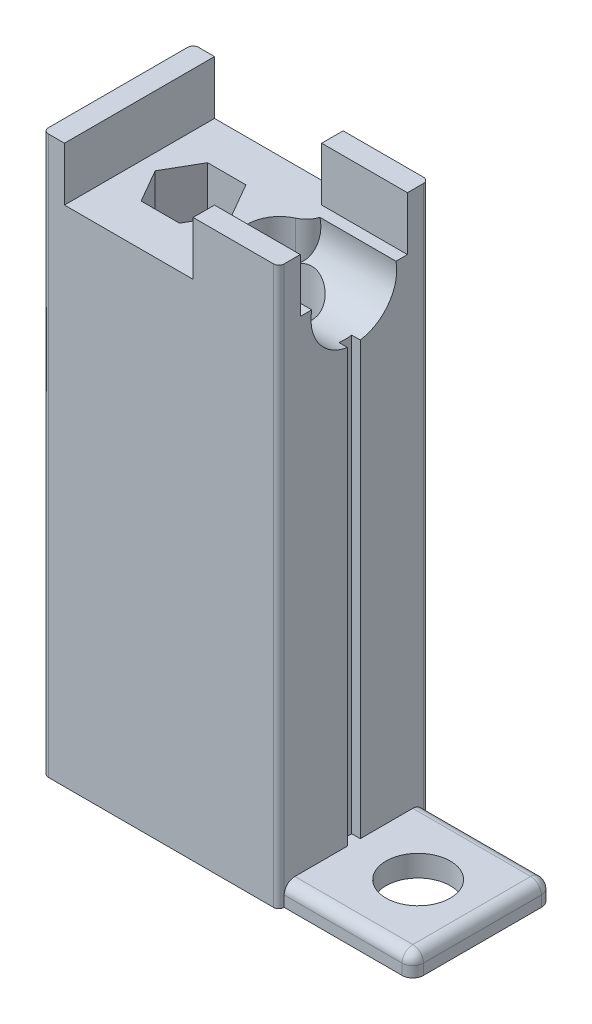
SolidWorks part; units mm, degrees
ref_plane "Front Plane" through (0, 0, 0) normal (0, 0, 1) x (1, 0, 0)
ref_plane "Top Plane" through (0, 0, 0) normal (0, 1, 0) x (1, 0, 0)
ref_plane "Right Plane" through (0, 0, 0) normal (1, 0, 0) x (0, 0, -1)
sketch "Sketch1" plane through (0, 0, 0) normal (0, 1, 0) x (1, 0, 0)
  line L1 (0, 0) -> (22, 0)
  line L2 (0, 0) -> (0, 14)
  line L3 (0, 14) -> (22, 14)
  line L4 (22, 0) -> (22, 14)
  dimension "D1" = 22
  dimension "D2" = 14
extrude "Boss-Extrude1" add sketch "Sketch1" along normal blind 47
sketch "Sketch2" plane through (0, 47, 0) normal (0, 1, 0) x (1, 0, 0)
  line L0 (22, 0) -> (22, 2)
  line L1 (22, 0) -> (22, 14) construction
  line L2 (0, 14) -> (2, 14)
  line L3 (22, 14) -> (0, 14) construction
  line L4 (2, 14) -> (2, 0)
  line L5 (22, 12) -> (22, 14)
  line L6 (0, 0) -> (22, 0) construction
  line L7 (0, 14) -> (0, 0)
  line L8 (2, 0) -> (0, 0)
  line L9 (22, 14) -> (14, 14)
  line L10 (14, 14) -> (14, 12)
  line L11 (14, 12) -> (22, 12)
  line L12 (22, 2) -> (14, 2)
  line L13 (14, 2) -> (14, 0)
  line L14 (14, 0) -> (22, 0)
  dimension "D1" = 2
  dimension "D2" = 2
  dimension "D3" = 8
  dimension "D4" = 8
  dimension "D5" = 2
extrude "Boss-Extrude2" add sketch "Sketch2" along normal blind 5
sketch "Sketch3" plane through (0, 47, 0) normal (0, 1, 0) x (1, 0, 0)
  line L1 (2, 0) -> (2, 14) construction
  line L2 (0, 7) -> (22, 7) construction
  line L4 (0, 14) -> (0, 0) construction
  line L5 (22, 2) -> (22, 12) construction
  line L7 (10.621, 7) -> (8.8312, 10.1)
  line L8 (8.8312, 10.1) -> (5.2517, 10.1)
  line L9 (5.2517, 10.1) -> (3.4619, 7)
  line L10 (3.4619, 7) -> (5.2517, 3.9)
  line L13 (5.2517, 3.9) -> (8.8312, 3.9)
  line L14 (8.8312, 3.9) -> (10.621, 7)
  circle A0 centre (7.0415, 7) radius 3.1 construction
  circle A1 centre (15.0829, 7) radius 3
  dimension "D1" = 6.2
  dimension "D2" = 5.0415
  dimension "D3" = 6
  dimension "D4" = 8.0415
extrude "Cut-Extrude1" cut sketch "Sketch3" against normal through all
sketch "Sketch4" plane through (22, 0, 0) normal (1, 0, 0) x (0, 0, -1)
  line L0 (7, 52) -> (7, 0) construction
  line L2 (0, 52) -> (14, 52) construction
  line L4 (0, 0) -> (14, 0) construction
  line L5 (0, 47) -> (14, 47) construction
  line L6 (6.4, 47) -> (7.6, 47)
  line L7 (6.4, 47) -> (6.4, 0)
  line L9 (6.4, 0) -> (7.6, 0)
  line L10 (7.6, 47) -> (7.6, 0)
  dimension "D1" = 1.2
  dimension "D2" = 0.6
extrude "Cut-Extrude2" cut sketch "Sketch4" against normal blind 0.8
sketch "Sketch5" plane through (22, 0, 0) normal (1, 0, 0) x (0, 0, -1)
  line L0 (7, 52) -> (7, 0) construction
  line L1 (0, 52) -> (14, 52) construction
  line L2 (6.4, 0) -> (7.6, 0) construction
  circle A0 centre (7, 46.25) radius 4
  dimension "D1" = 8
  dimension "D3" = 5.75
extrude "Cut-Extrude3" cut sketch "Sketch5" against normal blind 7
sketch "Sketch7" plane through (0, 0, 0) normal (-1, 0, 0) x (0, 0, 1)
  line L0 (-14, 52) -> (0, 52) construction
  line L2 (-14, 52) -> (-14, 0) construction
  text T0 "<b>Oufff</b>\r\n<b>TEAM</b>"
  dimension "D1" = 20
  dimension "D2" = 1
extrude "Cut-Extrude4" cut sketch "Sketch7" against normal blind 1
fillet "Fillet1" radius 2 2 edges at (15, 45.3015, -9.9989) (15, 45.3015, -4.0011)
fillet "Fillet2" radius 0.5 4 edges at (0, 26, -14) (22, 26, -14) (0, 26, 0) (22, 26, 0)
sketch "Sketch8" plane through (22, 0, 0) normal (1, 0, 0) x (0, 0, -1)
  line L1 (13.5, 0) -> (13.5, 52) construction
  line L2 (0.5, 0) -> (13.5, 0)
  line L3 (0.5, 0) -> (0.5, 2)
  line L4 (0.5, 2) -> (13.5, 2)
  line L7 (13.5, 0) -> (13.5, 2)
  dimension "D1" = 2
extrude "Boss-Extrude3" add sketch "Sketch8" along normal blind 12 and the other way blind 1
fillet "Fillet4" radius 1 5 edges at (34, 1, -13.5) (34, 1, -0.5) (28, 2, -13.5) (34, 2, -7) (28, 2, -0.5)
sketch "Sketch9" plane through (0, 2, 0) normal (0, 1, 0) x (1, 0, 0)
  line L0 (34, 7) -> (16.9331, 7) construction
  line L1 (34, 12.5) -> (34, 1.5) construction
  circle A0 centre (28, 7) radius 3
  dimension "D1" = 6
  dimension "D2" = 6
extrude "Cut-Extrude5" cut sketch "Sketch9" against normal through all
